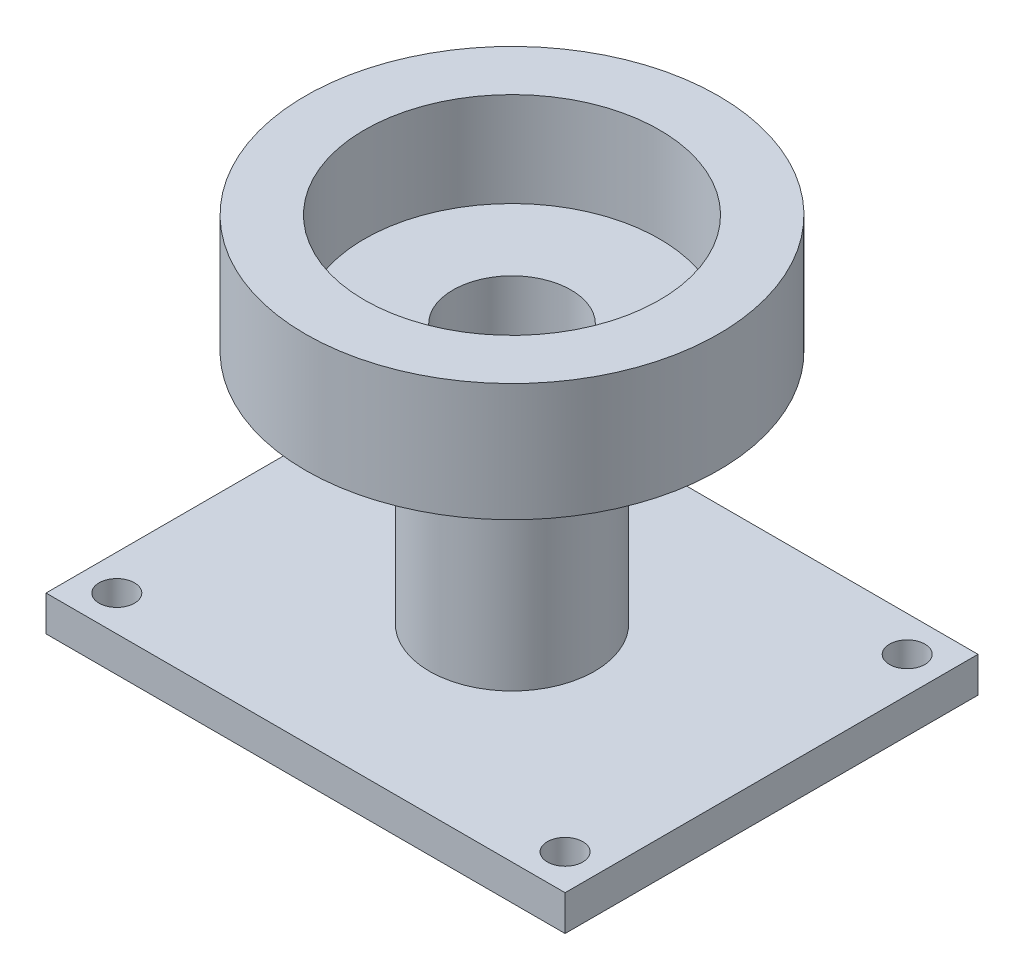
SolidWorks part; units mm, degrees
ref_plane "Front Plane" through (0, 0, 0) normal (0, 0, 1) x (1, 0, 0)
ref_plane "Top Plane" through (0, 0, 0) normal (0, 1, 0) x (1, 0, 0)
ref_plane "Right Plane" through (0, 0, 0) normal (1, 0, 0) x (0, 0, -1)
sketch "Sketch1" plane through (0, 0, 0) normal (0, 1, 0) x (1, 0, 0)
  circle A0 centre (0, 0) radius 17.5
  dimension "D1" = 35
extrude "Boss-Extrude1" add sketch "Sketch1" along normal blind 10
ref_plane "Plane1" through (0, 0, 0) normal (0, -1, 0) x (-1, 0, 0)
sketch "Sketch2" plane through (0, 0, 0) normal (0, -1, 0) x (-1, 0, 0)
  circle A0 centre (0, 0) radius 7
  dimension "D1" = 14
extrude "Boss-Extrude3" add sketch "Sketch2" along normal blind 20 contours A0
ref_plane "Plane3" through (0, 10, 0) normal (0, 1, 0) x (1, 0, 0)
sketch "Sketch5" plane through (0, 10, 0) normal (0, 1, 0) x (1, 0, 0)
  circle A0 centre (0, 0) radius 12.5
extrude "Cut-Extrude1" cut sketch "Sketch5" against normal blind 8
ref_plane "Plane4" through (0, 2, 0) normal (0, 1, 0) x (1, 0, 0)
sketch "Sketch6" plane through (0, 2, 0) normal (0, 1, 0) x (1, 0, 0)
  circle A0 centre (0, 0) radius 5
  dimension "D1" = 10
extrude "Cut-Extrude2" cut sketch "Sketch6" against normal blind 30
ref_plane "Plane10" through (0, -20, 0) normal (0, -1, 0) x (-1, 0, 0)
sketch "Sketch12" plane through (0, -20, 0) normal (0, -1, 0) x (-1, 0, 0)
  line L1 (-22, 17.5) -> (22, 17.5)
  line L2 (-22, 17.5) -> (-22, -17.5)
  line L3 (-22, -17.5) -> (22, -17.5)
  line L4 (22, 17.5) -> (22, -17.5)
  line L5 (-22, 17.5) -> (22, -17.5) construction
  line L6 (-22, -17.5) -> (22, 17.5) construction
  circle A1 centre (-19, -14.5) radius 1.5
  circle A2 centre (19, -14.5) radius 1.5
  circle A3 centre (19, 14.5) radius 1.5
  circle A4 centre (-19, 14.5) radius 1.5
  point P0 (0, 0)
  dimension "D1" = 44
  dimension "D3" = 3
  dimension "D2" = 35
  dimension "D4" = 3
  dimension "D5" = 2
  dimension "D6" = 2
extrude "Boss-Extrude4" add sketch "Sketch12" along normal blind 3 contours L2 L3 L4 L1
sketch "Sketch14" plane through (0, -20, 0) normal (0, -1, 0) x (-1, 0, 0)
  line L0 (-22, -17.5) -> (22, -17.5) construction
  line L1 (-22, 17.5) -> (-22, -17.5) construction
  circle A0 centre (-19, -14.5) radius 1.5
  circle A1 centre (19, -14.5) radius 1.5
  circle A2 centre (19, 14.5) radius 1.5
  circle A3 centre (-19, 14.5) radius 1.5
  dimension "D1" = 3
  dimension "D3" = 3
  dimension "D2" = 3
  dimension "D4" = 2
  dimension "D5" = 2
extrude "Cut-Extrude3" cut sketch "Sketch14" along normal blind 3
sketch "Sketch15" plane through (0, -20, 0) normal (0, -1, 0) x (-1, 0, 0)
  circle A0 centre (0, 0) radius 5
  dimension "D1" = 10
extrude "Cut-Extrude4" cut sketch "Sketch15" along normal blind 3
